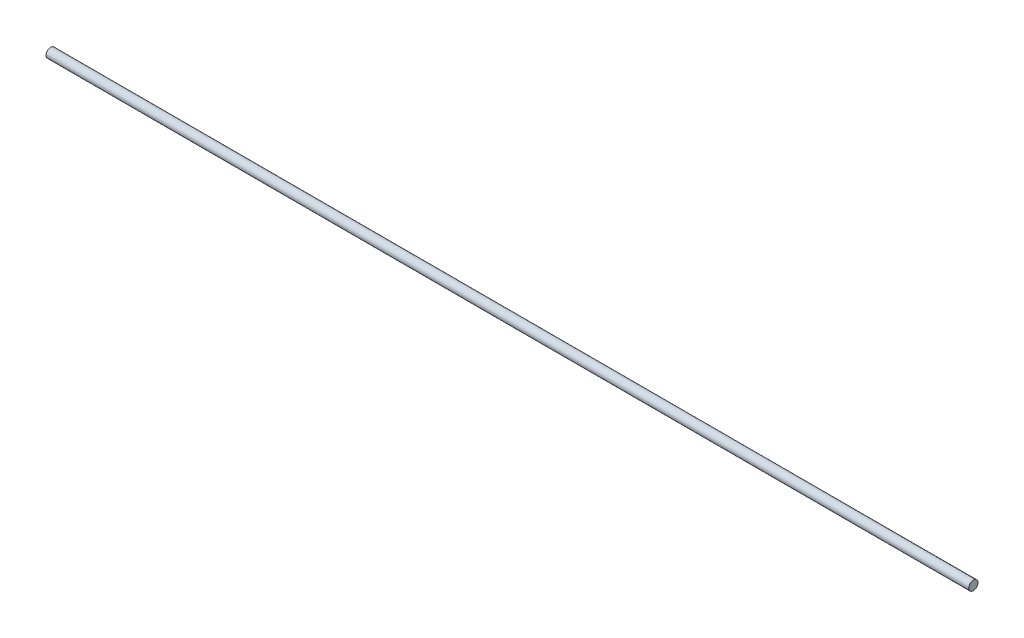
SolidWorks part; units mm, degrees
ref_plane "Alzado" through (0, 0, 0) normal (0, 0, 1) x (1, 0, 0)
ref_plane "Planta" through (0, 0, 0) normal (0, 1, 0) x (1, 0, 0)
ref_plane "Vista lateral" through (0, 0, 0) normal (1, 0, 0) x (0, 0, -1)
sketch "Croquis1" plane through (0, 0, 0) normal (1, 0, 0) x (0, 0, -1)
  circle A0 centre (0, 0) radius 4
  dimension "D1" = 8
extrude "Saliente-Extruir1" add sketch "Croquis1" along normal blind 795.2
